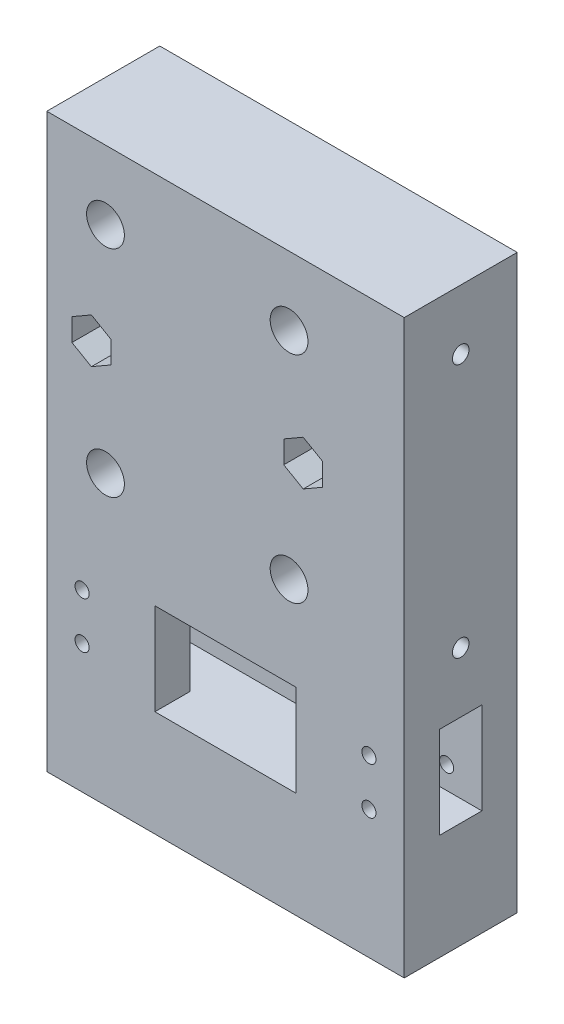
SolidWorks part; units mm, degrees
other "Markup1"
sketch "Sketch8" plane through (21.3115, 25, 0) normal (0.306, 0.1864, -0.9336) x (-0.9512, 0.0181, -0.3081)
ref_plane "Front Plane" through (0, 0, 0) normal (0, 0, 1) x (1, 0, 0)
ref_plane "Top Plane" through (0, 0, 0) normal (0, 1, 0) x (1, 0, 0)
ref_plane "Right Plane" through (0, 0, 0) normal (1, 0, 0) x (0, 0, -1)
sketch "Sketch1" plane through (0, 0, 0) normal (0, 0, 1) x (1, 0, 0)
  line L0 (0, 25) -> (0, -25) construction
  line L1 (21.3115, 25) -> (-21.3115, 25)
  line L2 (21.3115, 25) -> (21.3115, -25)
  line L3 (21.3115, -25) -> (-21.3115, -25)
  line L4 (-21.3115, 25) -> (-21.3115, -25)
  line L5 (21.3115, 25) -> (-21.3115, -25) construction
  line L6 (21.3115, -25) -> (-21.3115, 25) construction
  line L7 (-21.3115, 0) -> (21.3115, 0) construction
  circle A0 centre (-13, -15.25) radius 2.677
  circle A1 centre (13, -15.25) radius 2.677
  circle A2 centre (13, 15.25) radius 2.677
  circle A3 centre (-13, 15.25) radius 2.677
  point P0 (0, 0)
  dimension "D1" = 30.5
  dimension "D2" = 26
  dimension "D3" = 50
extrude "Boss-Extrude1" add sketch "Sketch1" along normal blind 16
sketch "Sketch2" plane through (0, 0, 0) normal (0, 0, 1) x (1, 0, 0)
  circle A0 centre (0, 0) radius 11
  dimension "D1" = 22
extrude "Cut-Extrude2" cut sketch "Sketch2" along normal blind 11
sketch "Sketch3" plane through (0, 0, 0) normal (0, 0, -1) x (-1, 0, 0)
  line L0 (0, 0) -> (-18.0234, 0) construction
  line L1 (0, 0) -> (0, 5.0894) construction
  circle A0 centre (-15, 0) radius 1.75
  circle A1 centre (15, 0) radius 1.75
  dimension "D1" = 15
  dimension "D2" = 3.5
extrude "Cut-Extrude3" cut sketch "Sketch3" against normal blind 10
sketch "Sketch9" plane through (0, 0, 0) normal (0, 0, -1) x (-1, 0, 0)
  line L0 (0, -11) -> (0, 11) construction
  line L1 (-15, 3.1754) -> (-17.75, 1.5877)
  line L2 (-17.75, 1.5877) -> (-17.75, -1.5877)
  line L3 (-17.75, -1.5877) -> (-15, -3.1754)
  line L4 (-15, -3.1754) -> (-12.25, -1.5877)
  line L5 (-12.25, -1.5877) -> (-12.25, 1.5877)
  line L6 (-12.25, 1.5877) -> (-15, 3.1754)
  line L7 (12.25, 1.5877) -> (15, 3.1754)
  line L8 (12.25, -1.5877) -> (12.25, 1.5877)
  line L9 (15, -3.1754) -> (12.25, -1.5877)
  line L10 (17.75, -1.5877) -> (15, -3.1754)
  line L11 (17.75, 1.5877) -> (17.75, -1.5877)
  line L12 (15, 3.1754) -> (17.75, 1.5877)
  circle A0 centre (-15, 0) radius 2.75 construction
  circle A1 centre (0, 0) radius 11 construction
  point P1 (-17.75, 0)
  dimension "D1" = 5.5
extrude "Cut-Extrude6" cut sketch "Sketch9" against normal through all from offset 5 offset against normal yes
sketch "Sketch10" plane through (0, 0, 0) normal (0, 0, 1) x (1, 0, 0)
  line L0 (21.3115, -25) -> (-21.3115, -25)
  line L1 (-21.3115, -25) -> (21.3115, -25) construction
  line L2 (-21.3115, -25) -> (-21.3115, -41)
  line L3 (-21.3115, -41) -> (21.3115, -41)
  line L4 (21.3115, -41) -> (21.3115, -25)
  dimension "D1" = 16
extrude "Boss-Extrude2" add sketch "Sketch10" along normal up to surface (16 mm away) up to face at (15, 0, 16)
sketch "Sketch14" plane through (-21.3115, 0, 0) normal (-1, 0, 0) x (0, 0, 1)
  line L0 (16, -41) -> (0, -41) construction
  line L1 (5, -41) -> (11, -41)
  line L2 (5, -41) -> (5, -28)
  line L3 (5, -28) -> (11, -28)
  line L4 (11, -41) -> (11, -28)
  line L7 (0, -41) -> (16, -41) construction
  point P6 (8, -41)
  point P7 (8, -41)
  dimension "D1" = 13
  dimension "D2" = 6
extrude "Cut-Extrude7" cut sketch "Sketch14" against normal through all
sketch "Sketch16" plane through (21.3115, 0, 0) normal (1, 0, 0) x (0, 0, -1)
  line L0 (-8, -28) -> (-8, 25)
  line L1 (-11, -28) -> (-5, -28) construction
  line L2 (-16, 25) -> (0, 25) construction
  line L3 (0, -41) -> (0, 25) construction
  line L4 (-16, 25) -> (0, 25)
  line L5 (-16, 25) -> (-16, -28)
  line L6 (-16, -28) -> (0, -28)
  line L7 (0, 25) -> (0, -28)
  line M6 (-11, -28) -> (-5, -28)
  line M9 (0, -41) -> (0, 25)
  line M10 (0, 25) -> (-16, 25)
  line M11 (-16, 25) -> (-16, -41)
extrude "Boss-Extrude3" add sketch "Sketch16" along normal blind 8 contours L6 L0 M11 M6 M10 | L6 L0 M6 M9 M10 region at (21.3115, -1.5, 12) region at (21.3115, -1.5, 4)
sketch "Sketch17" plane through (29.3115, 0, 0) normal (1, 0, 0) x (0, 0, -1)
  line L0 (-8, -28) -> (-8, 25)
  line L1 (-16, -28) -> (0, -28) construction
  line L2 (0, 25) -> (-16, 25) construction
  line L3 (-8, -1.5) -> (0, -1.5)
  line L4 (0, -28) -> (0, 25) construction
  circle A0 centre (-8, 16.5) radius 1.175
  circle A1 centre (-8, -19.5) radius 1.175
  point P8 (-8, -1.5)
  dimension "D2" = 2.35
  dimension "D1" = 18
extrude "Cut-Extrude9" cut sketch "Sketch17" against normal blind 8 contours L0 A0 | L0 A0 | A1 L0 | A1 L0 region at (29.3115, -19.5, 8.4987) region at (29.3115, 16.5, 8.4987) region at (29.3115, 16.5, 7.5013) region at (29.3115, -19.5, 7.5013)
sketch "Sketch18" plane through (0, 0, 0) normal (0, 0, -1) x (-1, 0, 0)
  line L0 (-25.3115, -28) -> (-25.3115, 25)
  line L1 (-29.3115, -28) -> (-21.3115, -28) construction
  line L2 (-29.3115, 25) -> (21.3115, 25) construction
  line L3 (-25.3115, -1.5) -> (-29.3115, -1.5)
  line L4 (-26.2115, 18.5) -> (-24.4115, 18.5)
  line L5 (-26.2115, 18.5) -> (-26.2115, 14.5)
  line L6 (-26.2115, 14.5) -> (-24.4115, 14.5)
  line L7 (-24.4115, 18.5) -> (-24.4115, 14.5)
  line L8 (-26.2115, 18.5) -> (-24.4115, 14.5) construction
  line L9 (-26.2115, 14.5) -> (-24.4115, 18.5) construction
  line L10 (-29.3115, -28) -> (-29.3115, 25) construction
  line L11 (-26.2115, -17.5) -> (-24.4115, -17.5)
  line L12 (-24.4115, -21.5) -> (-24.4115, -17.5)
  line L13 (-26.2115, -21.5) -> (-24.4115, -21.5)
  line L14 (-26.2115, -21.5) -> (-26.2115, -17.5)
  point P6 (-25.3115, 16.5)
  point P11 (-25.3115, -1.5)
  dimension "D1" = 18
  dimension "D2" = 4
  dimension "D3" = 1.8
extrude "Cut-Extrude10" cut sketch "Sketch18" against normal blind 10.2 contours L7 L4 L0 L6 | L5 L6 L0 L4 | L14 L11 L12 L13 region at (25.7615, 16.5, 0) region at (24.8615, 16.5, 0)
sketch "Sketch15" plane through (0, 0, 0) normal (0, 0, -1) x (-1, 0, 0)
  line L0 (21.3115, -41) -> (-21.3115, -41) construction
  line L1 (-29.3115, -23.2996) -> (21.3115, -23.2996)
  line L2 (-21.3115, -41) -> (-21.3115, -28)
  line L3 (-29.3115, -28) -> (-29.3115, 25) construction
  line L4 (-4, -23.2996) -> (-4, -41)
  line L7 (-21.3115, -41) -> (-21.3115, -28) construction
  line L8 (-21.3115, -28) -> (-21.3115, -41) construction
  line L9 (-21.3115, -34.5) -> (21.3115, -34.5)
  line L10 (21.3115, 25) -> (21.3115, -41) construction
  line L11 (21.3115, -34.5) -> (21.3115, -28)
  line L12 (21.3115, -28) -> (0, -28)
  line L13 (0, -28) -> (0, -41)
  circle A2 centre (16.3115, -37.8) radius 1
  circle A3 centre (16.3115, -31.2) radius 1
  point P11 (-21.3115, -41)
  dimension "D1" = 5
  dimension "D2" = 3.2
extrude "Cut-Extrude8" cut sketch "Sketch15" against normal through all and the other way through all contours A3 | A2
sketch "Sketch6" plane through (0, -41, 0) normal (0, -1, 0) x (1, 0, 0)
  line L1 (4.517, 11) -> (-4.517, 11)
  line L2 (4.517, 11) -> (4.517, 13.3875)
  line L3 (4.517, 13.3875) -> (-4.517, 13.3875)
  line L4 (-4.517, 11) -> (-4.517, 13.3875)
  line L5 (4.517, 11) -> (-4.517, 13.3875) construction
  line L6 (4.517, 13.3875) -> (-4.517, 11) construction
  point P0 (0, 12.1938)
  point P5 (0, 11)
  dimension "D1" = 11
  dimension "D2" = 9.034
extrude "Cut-Extrude5" cut sketch "Sketch6" against normal blind 20 and the other way through all
sketch "Sketch20" plane through (0, -28, 0) normal (0, -1, 0) x (-1, 0, 0)
  line L1 (-21.3115, -16) -> (-29.3115, -16)
  line L2 (-21.3115, -16) -> (-21.3115, 0)
  line L3 (-21.3115, 0) -> (-29.3115, 0)
  line L4 (-29.3115, -16) -> (-29.3115, 0)
extrude "Boss-Extrude5" add sketch "Sketch20" along normal up to surface (13 mm away) up to face at (0, -41, 12.8469)
sketch "Sketch21" plane through (0, -41, 0) normal (0, -1, 0) x (-1, 0, 0)
  line L0 (-29.3115, -16) -> (-29.3115, 0) construction
  line L1 (-21.3115, -11) -> (-29.3115, -11)
  line L2 (-21.3115, -11) -> (-21.3115, -5)
  line L3 (-21.3115, -5) -> (-29.3115, -5)
  line L4 (-29.3115, -11) -> (-29.3115, -5)
extrude "Cut-Extrude11" cut sketch "Sketch21" against normal up to surface (13 mm away) up to face at (0, -28, 9)
sketch "Sketch22" plane through (0, 0, 0) normal (0, 0, -1) x (-1, 0, 0)
  line L0 (21.3115, -41) -> (-29.3115, -41) construction
  line L1 (-29.3115, -41) -> (-29.3115, 25) construction
  circle A0 centre (-24.3115, -37.8) radius 1
  circle A3 centre (-24.3115, -31.2) radius 1
  dimension "D1" = 2
  dimension "D2" = 3.2
  dimension "D3" = 5
  dimension "D4" = 6.6
  dimension "D5" = 2
  dimension "D6" = 5
extrude "Cut-Extrude12" cut sketch "Sketch22" against normal through all
sketch "Sketch24" plane through (0, -41, 0) normal (0, -1, 0) x (1, 0, 0)
  line L1 (-21.3115, 5) -> (29.3115, 5)
  line L2 (-21.3115, 5) -> (-21.3115, 0)
  line L3 (-21.3115, 0) -> (29.3115, 0)
  line L4 (29.3115, 5) -> (29.3115, 0)
extrude "Boss-Extrude6" add sketch "Sketch24" along normal blind 15
sketch "Sketch25" plane through (0, 0, 5) normal (0, 0, 1) x (1, 0, 0)
  line L0 (29.3115, -56) -> (-21.3115, -56) construction
  line L1 (-21.3115, -56) -> (29.3115, -56)
  line L2 (-21.3115, -56) -> (-21.3115, -41)
  line L3 (-21.3115, -41) -> (29.3115, -41)
  line L4 (29.3115, -56) -> (29.3115, -41)
extrude "Boss-Extrude7" add sketch "Sketch25" along normal up to surface (11 mm away) up to face at (23.3115, -37.8, 16)
sketch "Sketch26" plane through (0, -56, 0) normal (0, -1, 0) x (1, 0, 0)
  line L0 (4, 16) -> (4, 0)
  line L1 (29.3115, 16) -> (-21.3115, 16) construction
  line L2 (-21.3115, 0) -> (29.3115, 0) construction
  line L3 (4, 8) -> (-21.3115, 8)
  line L4 (-21.3115, 16) -> (-21.3115, 0) construction
  circle A0 centre (-14, 8) radius 1
  circle A1 centre (22, 8) radius 1
  dimension "D1" = 2
  dimension "D2" = 18
extrude "Cut-Extrude13" cut sketch "Sketch26" against normal blind 10 contours L3 A0 | L3 A0 | A1 region at (-14, -56, 7.5756) region at (-14, -56, 8.4244) region at (22, -56, 8)
sketch "Sketch27" plane through (0, 0, 0) normal (0, 0, -1) x (-1, 0, 0)
  line L0 (-24.4115, -21.5) -> (-24.4115, -17.5) construction
  line L1 (-24.0015, -51.1) -> (-20.0015, -51.1)
  line L2 (-24.0015, -51.1) -> (-24.0015, -52.9)
  line L3 (-24.0015, -52.9) -> (-20.0015, -52.9)
  line L4 (-20.0015, -51.1) -> (-20.0015, -52.9)
  line L5 (-24.0015, -51.1) -> (-20.0015, -52.9) construction
  line L6 (-24.0015, -52.9) -> (-20.0015, -51.1) construction
  line L8 (-26.2115, -21.5) -> (-24.4115, -21.5) construction
  line L12 (-29.3115, -56) -> (-29.3115, 25) construction
  line L13 (21.3115, -56) -> (-29.3115, -56) construction
  line L14 (-29.3115, -49.5626) -> (21.3115, -49.5626)
  line L15 (21.3115, 25) -> (21.3115, -56) construction
  line L16 (-4, -49.5626) -> (-4, -56)
  line L17 (16.0015, -52.9) -> (12.0015, -52.9)
  line L18 (12.0015, -51.1) -> (12.0015, -52.9)
  line L19 (16.0015, -51.1) -> (12.0015, -51.1)
  line L20 (16.0015, -51.1) -> (16.0015, -52.9)
  point P0 (-22.0015, -52)
  dimension "D1" = 7.31
  dimension "D2" = 3.1
extrude "Cut-Extrude14" cut sketch "Sketch27" against normal blind 10.2 contours L4 L1 L2 L3 | L20 L19 L18 L17 region at (22.0015, -52, 0) region at (-14.0015, -52, 0)
sketch "Sketch29" plane through (0, 0, 16) normal (0, 0, 1) x (1, 0, 0)
  line L0 (-16.3115, -31.2) -> (24.3115, -37.8)
  line L1 (24.3115, -31.2) -> (-16.3115, -37.8)
  line L2 (-16.3115, -31.2) -> (24.3115, -31.2)
  line L3 (-16.3115, -31.2) -> (-16.3115, -37.8)
  line L4 (-16.3115, -37.8) -> (24.3115, -37.8)
  line L5 (24.3115, -31.2) -> (24.3115, -37.8)
  line L7 (-6, -28) -> (14, -28)
  line L8 (-6, -28) -> (-6, -41)
  line L9 (-6, -41) -> (14, -41)
  line L10 (14, -28) -> (14, -41)
  line L11 (-6, -28) -> (14, -41) construction
  line L12 (-6, -41) -> (14, -28) construction
  point P4 (4, -34.5)
  dimension "D1" = 13
  dimension "D2" = 20
extrude "Cut-Extrude15" cut sketch "Sketch29" against normal up to surface (5 mm away) contours L10 L7 L8 L2 | L10 L2 L8 L0 L1 | L0 L8 L1 | L10 L4 L8 L9 | L10 L0 L1 L8 L4 | L10 L1 L0 region at (4, -32.488, 16) region at (-2.6667, -34.5, 16) region at (4, -29.6, 16) region at (10.6667, -34.5, 16) region at (4, -36.512, 16) region at (4, -39.4, 16) up to face at (-16.3115, -32.2, 11)
